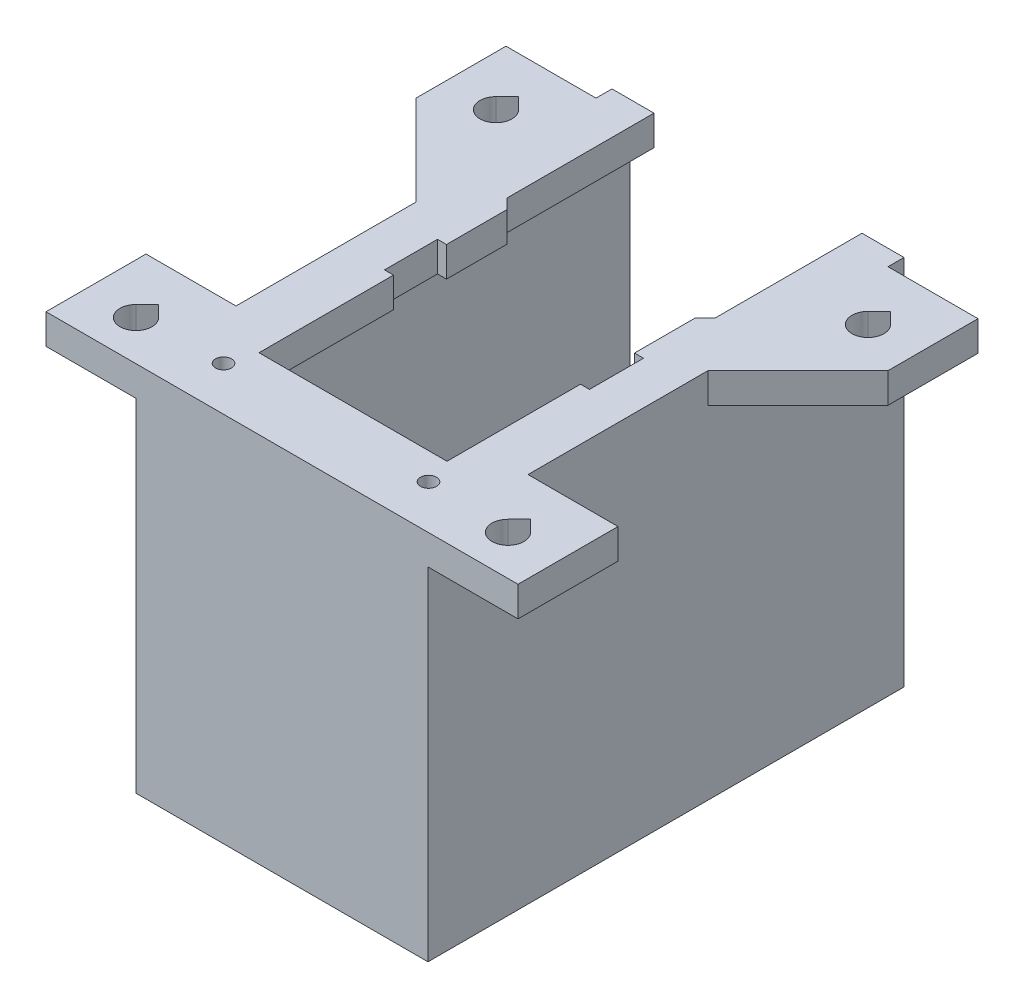
SolidWorks part; units mm, degrees
ref_plane "Front Plane" through (0, 0, 0) normal (0, 0, 1) x (1, 0, 0)
ref_plane "Top Plane" through (0, 0, 0) normal (0, 1, 0) x (1, 0, 0)
ref_plane "Right Plane" through (0, 0, 0) normal (1, 0, 0) x (0, 0, -1)
sketch "Sketch1" plane through (0, 0, 0) normal (0, 1, 0) x (1, 0, 0)
  line L0 (-9.2, -9.35) -> (9.2, -9.35) construction
  line L1 (-10.25, -12.25) -> (10.25, -12.25) construction
  line L2 (-10.25, -12.25) -> (-10.25, 12.25) construction
  line L3 (-10.25, 12.25) -> (10.25, 12.25) construction
  line L4 (10.25, -12.25) -> (10.25, 12.25) construction
  line L5 (-10.25, -12.25) -> (10.25, 12.25) construction
  line L6 (-10.25, 12.25) -> (10.25, -12.25) construction
  line L7 (0, -9.35) -> (0, 0) construction
  line L8 (-9.2, -9.35) -> (-9.2, 4) construction
  line L9 (-9.2, 4) -> (9.2, 4) construction
  line L10 (9.2, 4) -> (9.2, -9.35) construction
  line L11 (0, 8.05) -> (0, 0) construction
  line L12 (12.4, -14.65) -> (-12.4, -14.65) construction
  line L13 (12.4, -14.65) -> (12.4, 30.75) construction
  line L14 (12.4, 30.75) -> (-12.4, 30.75) construction
  line L15 (-12.4, -14.65) -> (-12.4, 30.75) construction
  line L16 (12.4, -14.65) -> (-12.4, 30.75) construction
  line L17 (12.4, 30.75) -> (-12.4, -14.65) construction
  line L18 (0, 20.55) -> (0, 8.05) construction
  line L19 (-9.4, -8.3) -> (-9.4, -16.65)
  line L20 (-7, -14.65) -> (7, -14.65) construction
  line L21 (-7, -14.65) -> (-7, 10.55) construction
  line L22 (-7, 10.55) -> (7, 10.55) construction
  line L23 (7, -14.65) -> (7, 10.55) construction
  line L24 (-7, -14.65) -> (7, 10.55) construction
  line L25 (-7, 10.55) -> (7, -14.65) construction
  line L26 (-14.6, -16.65) -> (14.6, -16.65)
  line L27 (-14.6, -16.65) -> (-14.6, 32.75)
  line L28 (-14.6, 32.75) -> (14.6, 32.75)
  line L29 (14.6, -16.65) -> (14.6, 32.75)
  line L30 (-14.6, -16.65) -> (14.6, 32.75) construction
  line L31 (-14.6, 32.75) -> (14.6, -16.65) construction
  line L32 (-12.8, -14.85) -> (12.8, -14.85)
  line L33 (-12.8, -14.85) -> (-12.8, 30.95)
  line L34 (-12.8, 30.95) -> (12.8, 30.95)
  line L35 (12.8, -14.85) -> (12.8, 30.95)
  line L36 (-12.8, -14.85) -> (12.8, 30.95) construction
  line L37 (-12.8, 30.95) -> (12.8, -14.85) construction
  line L38 (-7.2, -14.85) -> (7.2, -14.85) construction
  line L39 (-7.2, -14.85) -> (-7.2, 10.75)
  line L40 (-7.2, 10.75) -> (7.2, 10.75)
  line L41 (7.2, -14.85) -> (7.2, 10.75)
  line L42 (-7.2, -14.85) -> (7.2, 10.75) construction
  line L43 (-7.2, 10.75) -> (7.2, -14.85) construction
  line L44 (-9.4, -8.3) -> (9.4, -8.3) construction
  line L45 (-9.4, -8.3) -> (-9.4, 4.2)
  line L46 (-9.4, 4.2) -> (9.4, 4.2)
  line L47 (9.4, -8.3) -> (9.4, 4.2)
  line L48 (-9.4, -8.3) -> (9.4, 4.2) construction
  line L49 (-9.4, 4.2) -> (9.4, -8.3) construction
  line L50 (-7.2, -14.85) -> (-7.2, -16.65)
  line L51 (7.2, -14.85) -> (7.2, -16.65)
  line L52 (9.4, -8.3) -> (9.4, -16.65)
  line L53 (-12.8, -14.85) -> (-12.8, -16.65)
  line L54 (12.8, -14.85) -> (12.8, -16.65)
  line L55 (-12.8, -14.85) -> (-14.6, -14.85)
  line L56 (12.8, -14.85) -> (14.6, -14.85)
  line L57 (-10.3, 3.9) -> (-9.4, 3.9)
  line L58 (10.1, 9) -> (-10.1, 9) construction
  line L59 (10.1, 9) -> (10.1, 4) construction
  line L60 (10.1, 4) -> (-10.1, 4) construction
  line L61 (-10.1, 9) -> (-10.1, 4) construction
  line L62 (10.1, 9) -> (-10.1, 4) construction
  line L63 (10.1, 4) -> (-10.1, 9) construction
  line L64 (-10.3, 3.9) -> (-10.3, 9.2)
  line L65 (-10.3, 9.2) -> (10.3, 9.2)
  line L66 (10.3, 9.2) -> (10.3, 3.8)
  line L67 (10.3, 3.8) -> (9.4, 3.8)
  line L68 (-10.4, 30.95) -> (-10.4, 16.2422)
  line L69 (-10.4, 16.2422) -> (-4.9078, 10.75)
  line L70 (10.4, 16.2422) -> (4.9078, 10.75)
  line L71 (10.4, 30.95) -> (10.4, 16.2422)
  line L72 (-4.9078, 10.75) -> (-4.9078, 9.2)
  line L73 (4.9078, 10.75) -> (4.9078, 9.2)
  line L74 (-12.8, 30.95) -> (-12.8, 32.75)
  line L75 (12.8, 30.95) -> (12.8, 32.75)
  line L76 (-12.8, 30.95) -> (-14.6, 30.95)
  line L77 (12.8, 30.95) -> (14.6, 30.95)
  line L78 (-9.4, -9.55) -> (9.4, -9.55)
  line L79 (-9.4, 9.2) -> (-9.4, 15.2422)
  line L80 (9.4, 9.2) -> (9.4, 15.2422)
  line L81 (7.2, 10.75) -> (7.2, 13.0422)
  line L82 (-7.2, 10.75) -> (-7.2, 13.0422)
  circle A0 centre (-10.25, 12.25) radius 0.8
  circle A1 centre (10.25, 12.25) radius 0.8
  circle A2 centre (-10.25, -12.25) radius 0.8
  circle A3 centre (10.25, -12.25) radius 0.8
  circle A4 centre (0, 20.55) radius 10 construction
  circle A5 centre (0, 20.55) radius 10.4 construction
  circle A6 centre (-10.25, -8.45) radius 0.8
  circle A7 centre (10.25, -8.45) radius 0.8
  point P8 (0, 0)
  point P15 (0, -9.35)
  point P18 (0, 8.05)
  point P25 (0, -2.05)
  point P38 (0, -2.05)
  point P43 (0, -2.05)
  point P48 (0, 6.5)
  dimension "D1" = 1.6
  dimension "D9" = 2.4
  dimension "D11" = 20
  dimension "D27" = 0.2
  dimension "D30" = 6.2
  dimension "D2" = 24.5
  dimension "D3" = 20.5
  dimension "D4" = 18.4
  dimension "D5" = 2.9
  dimension "D6" = 13.35
  dimension "D7" = 24.8
  dimension "D8" = 45.4
  dimension "D10" = 10.2
  dimension "D12" = 14
  dimension "D13" = 1.8
  dimension "D14" = 1.8
  dimension "D15" = 0.4
  dimension "D16" = 0.4
  dimension "D17" = 0.2
  dimension "D18" = 0.2
  dimension "D19" = 0.2
  dimension "D20" = 0.2
  dimension "D21" = 5
  dimension "D22" = 20.2
  dimension "D23" = 0.2
  dimension "D24" = 0.2
  dimension "D25" = 0.2
  dimension "D26" = 45
  dimension "D28" = 0.2
  dimension "D29" = 0.2
extrude "Boss-Extrude2" add sketch "Sketch1" along normal blind 2 contours L33 L76 L27 L55 | L77 L35 L56 L29 | L56 L54 L26 L29 | L54 L32 L52 L26 | L52 L32 L41 L51 L26 | L51 L41 L32 L39 L50 L26 | L50 L39 L32 L19 L26 | L32 L53 L26 L19 | L53 L55 L27 L26 | L34 L71 L70 L40 L41 L65 L66 L47 L52 L32 L35 A3 A1 | L69 L68 L34 L33 L32 L19 L45 L64 L65 L39 L40 A2 A0 | L78 L19 L32 L39 | L78 L41 L32 L52 | L39 L82 L69 L79 L65 | L65 L64 L57 L45 L46 L39 | L19 L78 L39 L46 L45 | L41 L78 L52 L47 L46 | L67 L66 L65 L41 L46 L47 | L81 L41 L65 L80 L70 region at (-8.3, 0, 2.675) region at (-11.3268, 0, -6.8174) region at (-8.3, 0, 12.2) region at (-8.7688, 0, -6.6546) region at (-8.3, 0, 15.75) region at (-11.1, 0, 15.75) region at (-13.7, 0, -8.05) region at (-13.7, 0, 15.75) region at (0, 0, 15.75) region at (8.3, 0, 12.2) region at (8.3, 0, 2.675) region at (8.3, 0, 15.75) region at (-8.3816, 0, -11.7119) region at (8.775, 0, -6.6387) region at (11.3279, 0, -6.8195) region at (11.1, 0, 15.75) region at (8.3816, 0, -11.7119) region at (13.7, 0, 15.75) region at (13.7, 0, -8.05)
extrude "Boss-Extrude4" add sketch "Sketch1<6>" along normal offset from surface (35.2 mm away) 33.2 contours L33 L74 L28 L27 L55 | L77 L35 L56 L29 | L56 L54 L26 L29 | L54 L32 L52 L26 | L51 L41 L32 L39 L50 L26 | L32 L53 L26 L19 | L53 L55 L27 L26 | L50 L39 L32 L19 L26 | L52 L32 L41 L51 L26 region at (-8.3, 0, 15.75) region at (-11.1, 0, 15.75) region at (-13.7, 0, -8.05) region at (-13.7, 0, 15.75) region at (0, 0, 15.75) region at (8.3, 0, 15.75) region at (11.1, 0, 15.75) region at (13.7, 0, 15.75) region at (13.7, 0, -8.05) up to face at (0, 2, -9.9474) offset beyond the face yes
sketch "Sketch1<6>" plane through (0, 0, 0) normal (0, 1, 0) x (1, 0, 0) same geometry as "Sketch1"
extrude "Boss-Extrude7" add sketch "Sketch1<9>" along normal offset from surface (37.2 mm away) 2 contours L65 L79 L69 L68 L34 L33 L32 L19 L45 L57 L64 A2 A0 | L80 L65 L66 L67 L47 L52 L32 L35 L34 L71 L70 A3 A1 | L33 L76 L27 L55 | L53 L55 L27 L26 | L32 L53 L26 L19 | L50 L32 L19 L26 | L51 L32 L50 L26 | L52 L32 L51 L26 | L54 L32 L52 L26 | L56 L54 L26 L29 | L77 L35 L56 L29 | L78 L41 L32 L52 | L78 L19 L32 L39 | L78 L39 L32 L41 | A6 | A7 | A0 | A1 region at (-11.3268, 0, -6.8174) region at (-8.3, 0, 12.2) region at (-8.3, 0, 15.75) region at (-11.1, 0, 15.75) region at (0, 0, 12.2) region at (-13.7, 0, -8.05) region at (-13.7, 0, 15.75) region at (0, 0, 15.75) region at (8.3, 0, 12.2) region at (8.3, 0, 15.75) region at (11.3279, 0, -6.8195) region at (11.1, 0, 15.75) region at (13.7, 0, 15.75) region at (13.7, 0, -8.05) region at (-10.25, 0, -12.25) region at (10.25, 0, -12.25) region at (-10.25, 0, 8.45) region at (10.25, 0, 8.45) up to face at (0, 35.2, -7.6) offset beyond the face yes
sketch "Sketch1<9>" plane through (0, 0, 0) normal (0, 1, 0) x (1, 0, 0) same geometry as "Sketch1"
extrude "Cut-Extrude6" cut sketch "Sketch1<10>" along normal offset from surface (34.2 mm away) 3 contours L67 L66 L65 L41 L46 L47 | L65 L64 L57 L45 L46 L39 | L19 L78 L39 L46 L45 | L41 L78 L52 L47 L46 | L39 L82 L69 L79 L65 | L81 L41 L65 L80 L70 | L65 L79 L69 L68 L34 L33 L32 L19 L45 L57 L64 A2 A0 | L80 L65 L66 L67 L47 L52 L32 L35 L34 L71 L70 A3 A1 | L39 L78 L41 L46 | L78 L39 L32 L41 | L78 L19 L32 L39 | L78 L41 L32 L52 | A2 | A3 | A6 | A7 | A0 | A1 region at (-8.3, 0, 2.675) region at (-11.3268, 0, -6.8174) region at (-8.3, 0, 12.2) region at (-8.7688, 0, -6.6546) region at (0, 0, 12.2) region at (0, 0, 2.675) region at (8.3, 0, 12.2) region at (8.3, 0, 2.675) region at (-8.3816, 0, -11.7119) region at (8.775, 0, -6.6387) region at (11.3279, 0, -6.8195) region at (8.3816, 0, -11.7119) region at (-10.25, 0, -12.25) region at (10.25, 0, -12.25) region at (-10.25, 0, 12.25) region at (10.25, 0, 12.25) region at (-10.25, 0, 8.45) region at (10.25, 0, 8.45) up to face at (10.25, 37.2, 13.05)
sketch "Sketch1<10>" plane through (0, 0, 0) normal (0, 1, 0) x (1, 0, 0) same geometry as "Sketch1"
extrude "Boss-Extrude8" add sketch "Sketch1<11>" along normal offset from surface (2 mm away) 2 contours L80 L65 L66 L67 L47 L52 L32 L35 L34 L71 L70 A3 A1 | L78 L41 L32 L52 | L65 L79 L69 L68 L34 L33 L32 L19 L45 L57 L64 A2 A0 | L78 L19 L32 L39 | L67 L66 L65 L41 L46 L47 | L41 L78 L52 L47 L46 | L65 L64 L57 L45 L46 L39 | L19 L78 L39 L46 L45 | L39 L82 L69 L79 L65 | L81 L41 L65 L80 L70 | A3 | A2 region at (-8.3, 0, 2.675) region at (-11.3268, 0, -6.8174) region at (-8.3, 0, 12.2) region at (-8.7688, 0, -6.6546) region at (8.3, 0, 12.2) region at (8.3, 0, 2.675) region at (-8.3816, 0, -11.7119) region at (8.775, 0, -6.6387) region at (11.3279, 0, -6.8195) region at (8.3816, 0, -11.7119) region at (-10.25, 0, 12.25) region at (10.25, 0, 12.25) up to face at (0, 0, -7.6)
sketch "Sketch1<11>" plane through (0, 0, 0) normal (0, 1, 0) x (1, 0, 0) same geometry as "Sketch1"
sketch "Sketch2" plane through (0, 37.2, 0) normal (0, 1, 0) x (1, 0, 0)
  line L0 (-18.6, 23.35) -> (18.6, 23.35) construction
  line L1 (0, 23.35) -> (0, 0) construction
  line L2 (-14.6, 29.35) -> (-23.6, 29.35)
  line L3 (-14.6, -16.65) -> (-14.6, 30.95) construction
  line L4 (-23.6, 29.35) -> (-23.6, 21.35)
  line L5 (-23.6, 21.35) -> (-14.6, 21.35)
  line L6 (-14.6, 21.35) -> (-14.6, 29.35)
  line L7 (23.6, 29.35) -> (23.6, 21.35)
  line L8 (23.6, 21.35) -> (14.6, 21.35)
  line L9 (14.6, 21.35) -> (14.6, 29.35)
  line L10 (14.6, 29.35) -> (23.6, 29.35)
  line L12 (-19.7314, 24.4814) -> (-18.6, 25.6127)
  line L13 (-18.6, 25.6127) -> (-17.4686, 24.4814)
  line L14 (-18.6, 25.6127) -> (-18.6, 23.35) construction
  line L15 (19.7314, 24.4814) -> (18.6, 25.6127)
  line L16 (18.6, 25.6127) -> (17.4686, 24.4814)
  line L17 (-14.6, -16.65) -> (-23.6, -16.65)
  line L18 (-23.6, -16.65) -> (-23.6, -6.65)
  line L19 (-23.6, -6.65) -> (-14.6, -6.65)
  line L20 (-18.6, -12.65) -> (-18.6, 23.35) construction
  line L21 (-18.6, -10.3873) -> (-19.7314, -11.5186)
  line L22 (-18.6, -10.3873) -> (-17.4686, -11.5186)
  line L23 (-14.6, -16.65) -> (-14.6, -6.65)
  line L24 (18.6, -10.3873) -> (19.7314, -11.5186)
  line L25 (18.6, -10.3873) -> (17.4686, -11.5186)
  line L26 (14.6, -16.65) -> (14.6, -6.65)
  line L27 (14.6, -16.65) -> (23.6, -16.65)
  line L28 (23.6, -16.65) -> (23.6, -6.65)
  line L29 (23.6, -6.65) -> (14.6, -6.65)
  line L30 (-14.6, -16.65) -> (14.6, -16.65) construction
  circle A0 centre (-18.6, 23.35) radius 1.6
  circle A1 centre (18.6, 23.35) radius 1.6
  circle A2 centre (-18.6, -12.65) radius 1.6
  circle A3 centre (18.6, -12.65) radius 1.6
  point P44 (-14.6, -3.3638)
  line M11 (-14.6, 30.95) -> (-14.6, -16.65)
  line M13 (14.6, -16.65) -> (14.6, 30.95)
  dimension "D1" = 3.2
  dimension "D2" = 4
  dimension "D3" = 5
  dimension "D7" = 90
  dimension "D8" = 4
  dimension "D9" = 6
  dimension "D11" = 36
  dimension "D4" = 6
  dimension "D5" = 90
  dimension "D6" = 2
  dimension "D10" = 5
extrude "Boss-Extrude9" add sketch "Sketch2" against normal blind 3 contours L10 L8 L7 A1 M13 | L4 L5 L2 A0 L12 L13 M11 | L19 L18 L17 A2 L21 L22 M11 | L28 L29 L27 L24 A3 L25 M13 region at (-19.1678, 37.2, -25.6058) region at (-14.7345, 37.2, 11.65) region at (19.1, 37.2, 6.7845) region at (19.1678, 37.2, -25.6058)
chamfer "Chamfer1" distance 10 angle 45 2 edges at (14.6, 35.7, -21.35) (-14.6, 35.7, -21.35)
